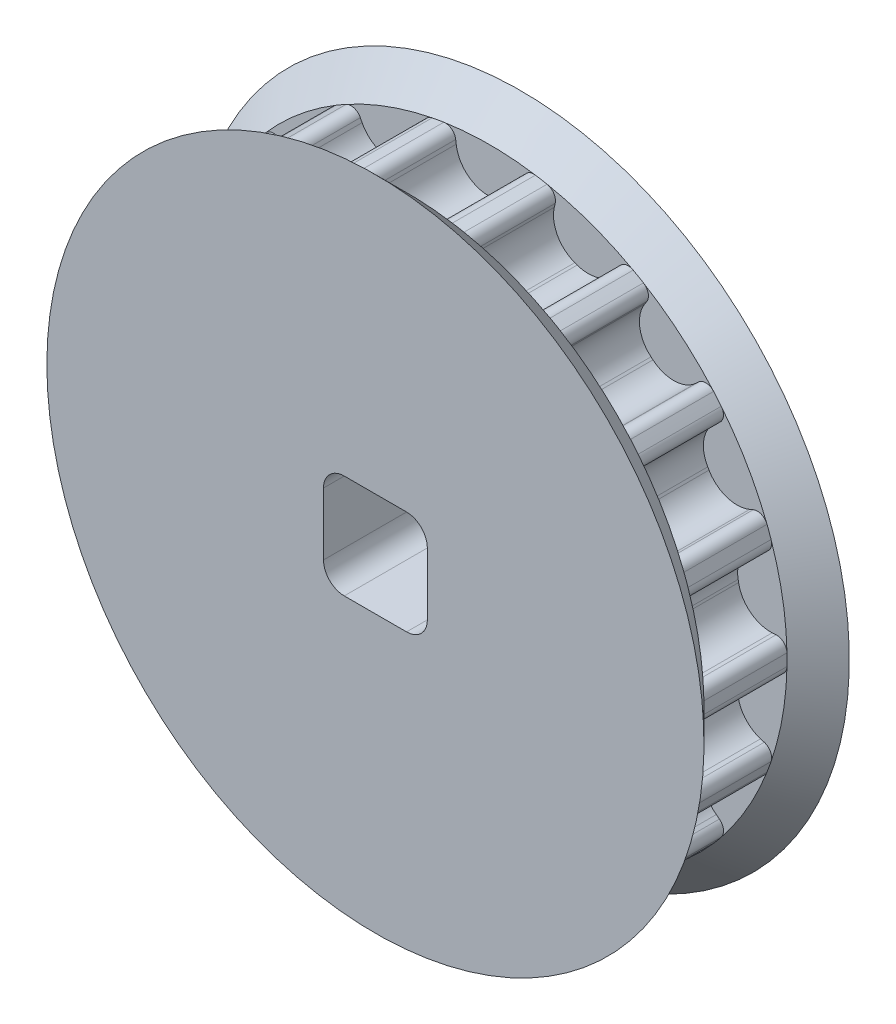
SolidWorks part; units mm, degrees
ref_plane "前视基准面" through (0, 0, 0) normal (0, 0, 1) x (1, 0, 0)
ref_plane "上视基准面" through (0, 0, 0) normal (0, 1, 0) x (1, 0, 0)
ref_plane "右视基准面" through (0, 0, 0) normal (1, 0, 0) x (0, 0, -1)
sketch "草图1" plane through (0, 0, 0) normal (0, 0, 1) x (1, 0, 0)
  line L0 (0, 0) -> (0, 14.3239) construction
  line L1 (0, 0) -> (-2.4873, 14.1063) construction
  line L2 (0, 0) -> (2.4873, 14.1063) construction
  line L3 (-1000, 12.1639) -> (49000, 12.1639) construction
  line L4 (-1.625, 14.2315) -> (-1.625, 13.6556) construction
  line L5 (-1.6329, 13.7199) -> (-1.61, 13.5338)
  line L6 (-0.0617, 12.1639) -> (0.0617, 12.1639)
  line L7 (1.6329, 13.7199) -> (1.61, 13.5338)
  line L8 (3.1581, 13.451) -> (3.1159, 13.2683)
  line L9 (4.1024, 11.4515) -> (4.2183, 11.4093)
  line L10 (6.2269, 12.334) -> (6.1418, 12.167)
  line L11 (7.5681, 11.5597) -> (7.466, 11.4024)
  line L12 (7.7716, 9.3578) -> (7.8661, 9.2785)
  line L13 (10.0699, 9.4605) -> (9.9327, 9.3326)
  line L14 (11.0654, 8.2741) -> (10.9156, 8.1613)
  line L15 (10.5034, 6.1354) -> (10.5651, 6.0286)
  line L16 (12.6983, 5.4458) -> (12.5257, 5.3726)
  line L17 (13.2279, 3.9905) -> (13.0486, 3.9357)
  line L18 (11.9684, 2.173) -> (11.9899, 2.0515)
  line L19 (13.795, 0.7743) -> (13.6078, 0.7645)
  line L20 (13.795, -0.7743) -> (13.6078, -0.7645)
  line L21 (11.9899, -2.0515) -> (11.9684, -2.173)
  line L22 (13.2279, -3.9905) -> (13.0486, -3.9357)
  line L23 (12.6983, -5.4458) -> (12.5257, -5.3726)
  line L24 (10.5651, -6.0286) -> (10.5034, -6.1354)
  line L25 (11.0654, -8.2741) -> (10.9156, -8.1613)
  line L26 (10.0699, -9.4605) -> (9.9327, -9.3326)
  line L27 (7.8661, -9.2785) -> (7.7716, -9.3578)
  line L28 (7.5681, -11.5597) -> (7.466, -11.4024)
  line L29 (6.2269, -12.334) -> (6.1418, -12.167)
  line L30 (4.2183, -11.4093) -> (4.1024, -11.4515)
  line L31 (3.1581, -13.451) -> (3.1159, -13.2683)
  line L32 (1.6329, -13.7199) -> (1.61, -13.5338)
  line L33 (0.0617, -12.1639) -> (-0.0617, -12.1639)
  line L34 (-1.6329, -13.7199) -> (-1.61, -13.5338)
  line L35 (-3.1581, -13.451) -> (-3.1159, -13.2683)
  line L36 (-4.1024, -11.4515) -> (-4.2183, -11.4093)
  line L37 (-6.2269, -12.334) -> (-6.1418, -12.167)
  line L38 (-7.5681, -11.5597) -> (-7.466, -11.4024)
  line L39 (-7.7716, -9.3578) -> (-7.8661, -9.2785)
  line L40 (-10.0699, -9.4605) -> (-9.9327, -9.3326)
  line L41 (-11.0654, -8.2741) -> (-10.9156, -8.1613)
  line L42 (-10.5034, -6.1354) -> (-10.5651, -6.0286)
  line L43 (-12.6983, -5.4458) -> (-12.5257, -5.3726)
  line L44 (-13.2279, -3.9905) -> (-13.0486, -3.9357)
  line L45 (-11.9684, -2.173) -> (-11.9899, -2.0515)
  line L46 (-13.795, -0.7743) -> (-13.6078, -0.7645)
  line L47 (-13.795, 0.7743) -> (-13.6078, 0.7645)
  line L48 (-11.9899, 2.0515) -> (-11.9684, 2.173)
  line L49 (-13.2279, 3.9905) -> (-13.0486, 3.9357)
  line L50 (-12.6983, 5.4458) -> (-12.5257, 5.3726)
  line L51 (-10.5651, 6.0286) -> (-10.5034, 6.1354)
  line L52 (-11.0654, 8.2741) -> (-10.9156, 8.1613)
  line L53 (-10.0699, 9.4605) -> (-9.9327, 9.3326)
  line L54 (-7.8661, 9.2785) -> (-7.7716, 9.3578)
  line L55 (-7.5681, 11.5597) -> (-7.466, 11.4024)
  line L56 (-6.2269, 12.334) -> (-6.1418, 12.167)
  line L57 (-4.2183, 11.4093) -> (-4.1024, 11.4515)
  line L58 (-3.1581, 13.451) -> (-3.1159, 13.2683)
  arc A0 (2.4873, 14.1063) -> (-2.4873, 14.1063) centre (0, 0) ccw construction
  circle A1 centre (0, 0) radius 13.7519 construction
  arc A2 (-2.4873, 14.1063) -> (-2.2062, 14.153) centre (0, 0) cw
  arc A3 (-1.6329, 13.7199) -> (-2.2062, 14.153) centre (-2.1292, 13.659) ccw
  arc A4 (-1.61, 13.5338) -> (-0.0617, 12.1639) centre (-0.0617, 13.7239) ccw
  arc A5 (1.61, 13.5338) -> (0.0617, 12.1639) centre (0.0617, 13.7239) cw
  arc A6 (1.6329, 13.7199) -> (2.2062, 14.153) centre (2.1292, 13.659) cw
  arc A7 (2.4873, 14.1063) -> (2.2062, 14.153) centre (0, 0) ccw
  arc A8 (2.4873, 14.1063) -> (2.7675, 14.0541) centre (0, 0) cw
  arc A9 (3.1581, 13.451) -> (2.7675, 14.0541) centre (2.6709, 13.5635) ccw
  arc A10 (3.1159, 13.2683) -> (4.1024, 11.4515) centre (4.6359, 12.9174) ccw
  arc A11 (6.1418, 12.167) -> (4.2183, 11.4093) centre (4.7518, 12.8752) cw
  arc A12 (6.2269, 12.334) -> (6.9138, 12.5449) centre (6.6724, 12.107) cw
  arc A13 (7.162, 12.4049) -> (6.9138, 12.5449) centre (0, 0) ccw
  arc A14 (7.162, 12.4049) -> (7.4074, 12.26) centre (0, 0) cw
  arc A15 (7.5681, 11.5597) -> (7.4074, 12.26) centre (7.1488, 11.832) ccw
  arc A16 (7.466, 11.4024) -> (7.7716, 9.3578) centre (8.7743, 10.5528) ccw
  arc A17 (9.9327, 9.3326) -> (7.8661, 9.2785) centre (8.8688, 10.4735) cw
  arc A18 (10.0699, 9.4605) -> (10.7874, 9.4237) centre (10.4109, 9.0948) cw
  arc A19 (10.9728, 9.2073) -> (10.7874, 9.4237) centre (0, 0) ccw
  arc A20 (10.9728, 9.2073) -> (11.1538, 8.9871) centre (0, 0) cw
  arc A21 (11.0654, 8.2741) -> (11.1538, 8.9871) centre (10.7644, 8.6734) ccw
  arc A22 (10.9156, 8.1613) -> (10.5034, 6.1354) centre (11.8544, 6.9154) ccw
  arc A23 (12.5257, 5.3726) -> (10.5651, 6.0286) centre (11.9161, 6.8086) cw
  arc A24 (12.6983, 5.4458) -> (13.36, 5.1659) centre (12.8936, 4.9856) cw
  arc A25 (13.4601, 4.8991) -> (13.36, 5.1659) centre (0, 0) ccw
  arc A26 (13.4601, 4.8991) -> (13.5549, 4.6303) centre (0, 0) cw
  arc A27 (13.2279, 3.9905) -> (13.5549, 4.6303) centre (13.0818, 4.4687) ccw
  arc A28 (13.0486, 3.9357) -> (11.9684, 2.173) centre (13.5047, 2.4439) ccw
  arc A29 (13.6078, 0.7645) -> (11.9899, 2.0515) centre (13.5262, 2.3224) cw
  arc A30 (13.795, 0.7743) -> (14.3211, 0.285) centre (13.8212, 0.275) cw
  arc A31 (14.3239, 0) -> (14.3211, 0.285) centre (0, 0) ccw
  arc A32 (14.3239, 0) -> (14.3211, -0.285) centre (0, 0) cw
  arc A33 (13.795, -0.7743) -> (14.3211, -0.285) centre (13.8212, -0.275) ccw
  arc A34 (13.6078, -0.7645) -> (11.9899, -2.0515) centre (13.5262, -2.3224) ccw
  arc A35 (13.0486, -3.9357) -> (11.9684, -2.173) centre (13.5047, -2.4439) cw
  arc A36 (13.2279, -3.9905) -> (13.5549, -4.6303) centre (13.0818, -4.4687) cw
  arc A37 (13.4601, -4.8991) -> (13.5549, -4.6303) centre (0, 0) ccw
  arc A38 (13.4601, -4.8991) -> (13.36, -5.1659) centre (0, 0) cw
  arc A39 (12.6983, -5.4458) -> (13.36, -5.1659) centre (12.8936, -4.9856) ccw
  arc A40 (12.5257, -5.3726) -> (10.5651, -6.0286) centre (11.9161, -6.8086) ccw
  arc A41 (10.9156, -8.1613) -> (10.5034, -6.1354) centre (11.8544, -6.9154) cw
  arc A42 (11.0654, -8.2741) -> (11.1538, -8.9871) centre (10.7644, -8.6734) cw
  arc A43 (10.9728, -9.2073) -> (11.1538, -8.9871) centre (0, 0) ccw
  arc A44 (10.9728, -9.2073) -> (10.7874, -9.4237) centre (0, 0) cw
  arc A45 (10.0699, -9.4605) -> (10.7874, -9.4237) centre (10.4109, -9.0948) ccw
  arc A46 (9.9327, -9.3326) -> (7.8661, -9.2785) centre (8.8688, -10.4735) ccw
  arc A47 (7.466, -11.4024) -> (7.7716, -9.3578) centre (8.7743, -10.5528) cw
  arc A48 (7.5681, -11.5597) -> (7.4074, -12.26) centre (7.1488, -11.832) cw
  arc A49 (7.162, -12.4049) -> (7.4074, -12.26) centre (0, 0) ccw
  arc A50 (7.162, -12.4049) -> (6.9138, -12.5449) centre (0, 0) cw
  arc A51 (6.2269, -12.334) -> (6.9138, -12.5449) centre (6.6724, -12.107) ccw
  arc A52 (6.1418, -12.167) -> (4.2183, -11.4093) centre (4.7518, -12.8752) ccw
  arc A53 (3.1159, -13.2683) -> (4.1024, -11.4515) centre (4.6359, -12.9174) cw
  arc A54 (3.1581, -13.451) -> (2.7675, -14.0541) centre (2.6709, -13.5635) cw
  arc A55 (2.4873, -14.1063) -> (2.7675, -14.0541) centre (0, 0) ccw
  arc A56 (2.4873, -14.1063) -> (2.2062, -14.153) centre (0, 0) cw
  arc A57 (1.6329, -13.7199) -> (2.2062, -14.153) centre (2.1292, -13.659) ccw
  arc A58 (1.61, -13.5338) -> (0.0617, -12.1639) centre (0.0617, -13.7239) ccw
  arc A59 (-1.61, -13.5338) -> (-0.0617, -12.1639) centre (-0.0617, -13.7239) cw
  arc A60 (-1.6329, -13.7199) -> (-2.2062, -14.153) centre (-2.1292, -13.659) cw
  arc A61 (-2.4873, -14.1063) -> (-2.2062, -14.153) centre (0, 0) ccw
  arc A62 (-2.4873, -14.1063) -> (-2.7675, -14.0541) centre (0, 0) cw
  arc A63 (-3.1581, -13.451) -> (-2.7675, -14.0541) centre (-2.6709, -13.5635) ccw
  arc A64 (-3.1159, -13.2683) -> (-4.1024, -11.4515) centre (-4.6359, -12.9174) ccw
  arc A65 (-6.1418, -12.167) -> (-4.2183, -11.4093) centre (-4.7518, -12.8752) cw
  arc A66 (-6.2269, -12.334) -> (-6.9138, -12.5449) centre (-6.6724, -12.107) cw
  arc A67 (-7.162, -12.4049) -> (-6.9138, -12.5449) centre (0, 0) ccw
  arc A68 (-7.162, -12.4049) -> (-7.4074, -12.26) centre (0, 0) cw
  arc A69 (-7.5681, -11.5597) -> (-7.4074, -12.26) centre (-7.1488, -11.832) ccw
  arc A70 (-7.466, -11.4024) -> (-7.7716, -9.3578) centre (-8.7743, -10.5528) ccw
  arc A71 (-9.9327, -9.3326) -> (-7.8661, -9.2785) centre (-8.8688, -10.4735) cw
  arc A72 (-10.0699, -9.4605) -> (-10.7874, -9.4237) centre (-10.4109, -9.0948) cw
  arc A73 (-10.9728, -9.2073) -> (-10.7874, -9.4237) centre (0, 0) ccw
  arc A74 (-10.9728, -9.2073) -> (-11.1538, -8.9871) centre (0, 0) cw
  arc A75 (-11.0654, -8.2741) -> (-11.1538, -8.9871) centre (-10.7644, -8.6734) ccw
  arc A76 (-10.9156, -8.1613) -> (-10.5034, -6.1354) centre (-11.8544, -6.9154) ccw
  arc A77 (-12.5257, -5.3726) -> (-10.5651, -6.0286) centre (-11.9161, -6.8086) cw
  arc A78 (-12.6983, -5.4458) -> (-13.36, -5.1659) centre (-12.8936, -4.9856) cw
  arc A79 (-13.4601, -4.8991) -> (-13.36, -5.1659) centre (0, 0) ccw
  arc A80 (-13.4601, -4.8991) -> (-13.5549, -4.6303) centre (0, 0) cw
  arc A81 (-13.2279, -3.9905) -> (-13.5549, -4.6303) centre (-13.0818, -4.4687) ccw
  arc A82 (-13.0486, -3.9357) -> (-11.9684, -2.173) centre (-13.5047, -2.4439) ccw
  arc A83 (-13.6078, -0.7645) -> (-11.9899, -2.0515) centre (-13.5262, -2.3224) cw
  arc A84 (-13.795, -0.7743) -> (-14.3211, -0.285) centre (-13.8212, -0.275) cw
  arc A85 (-14.3239, 0) -> (-14.3211, -0.285) centre (0, 0) ccw
  arc A86 (-14.3239, 0) -> (-14.3211, 0.285) centre (0, 0) cw
  arc A87 (-13.795, 0.7743) -> (-14.3211, 0.285) centre (-13.8212, 0.275) ccw
  arc A88 (-13.6078, 0.7645) -> (-11.9899, 2.0515) centre (-13.5262, 2.3224) ccw
  arc A89 (-13.0486, 3.9357) -> (-11.9684, 2.173) centre (-13.5047, 2.4439) cw
  arc A90 (-13.2279, 3.9905) -> (-13.5549, 4.6303) centre (-13.0818, 4.4687) cw
  arc A91 (-13.4601, 4.8991) -> (-13.5549, 4.6303) centre (0, 0) ccw
  arc A92 (-13.4601, 4.8991) -> (-13.36, 5.1659) centre (0, 0) cw
  arc A93 (-12.6983, 5.4458) -> (-13.36, 5.1659) centre (-12.8936, 4.9856) ccw
  arc A94 (-12.5257, 5.3726) -> (-10.5651, 6.0286) centre (-11.9161, 6.8086) ccw
  arc A95 (-10.9156, 8.1613) -> (-10.5034, 6.1354) centre (-11.8544, 6.9154) cw
  arc A96 (-11.0654, 8.2741) -> (-11.1538, 8.9871) centre (-10.7644, 8.6734) cw
  arc A97 (-10.9728, 9.2073) -> (-11.1538, 8.9871) centre (0, 0) ccw
  arc A98 (-10.9728, 9.2073) -> (-10.7874, 9.4237) centre (0, 0) cw
  arc A99 (-10.0699, 9.4605) -> (-10.7874, 9.4237) centre (-10.4109, 9.0948) ccw
  arc A100 (-9.9327, 9.3326) -> (-7.8661, 9.2785) centre (-8.8688, 10.4735) ccw
  arc A101 (-7.466, 11.4024) -> (-7.7716, 9.3578) centre (-8.7743, 10.5528) cw
  arc A102 (-7.5681, 11.5597) -> (-7.4074, 12.26) centre (-7.1488, 11.832) cw
  arc A103 (-7.162, 12.4049) -> (-7.4074, 12.26) centre (0, 0) ccw
  arc A104 (-7.162, 12.4049) -> (-6.9138, 12.5449) centre (0, 0) cw
  arc A105 (-6.2269, 12.334) -> (-6.9138, 12.5449) centre (-6.6724, 12.107) ccw
  arc A106 (-6.1418, 12.167) -> (-4.2183, 11.4093) centre (-4.7518, 12.8752) ccw
  arc A107 (-3.1159, 13.2683) -> (-4.1024, 11.4515) centre (-4.6359, 12.9174) cw
  arc A108 (-3.1581, 13.451) -> (-2.7675, 14.0541) centre (-2.6709, 13.5635) cw
  arc A109 (-2.4873, 14.1063) -> (-2.7675, 14.0541) centre (0, 0) ccw
  point P17 (-1.6947, 14.2233)
  point P20 (-1.4418, 12.1639)
  point P22 (0, 12.1639)
  point P38 (4.1603, 11.4304)
  point P53 (7.8188, 9.3181)
  point P68 (10.5343, 6.082)
  point P83 (11.9791, 2.1122)
  point P98 (11.9791, -2.1122)
  point P113 (10.5343, -6.082)
  point P128 (7.8188, -9.3181)
  point P143 (4.1603, -11.4304)
  point P158 (0, -12.1639)
  point P173 (-4.1603, -11.4304)
  point P188 (-7.8188, -9.3181)
  point P193 (0, 0)
  point P202 (-10.5343, -6.082)
  point P217 (-11.9791, -2.1122)
  point P232 (-11.9791, 2.1122)
  point P247 (-10.5343, 6.082)
  point P262 (-7.8188, 9.3181)
  point P277 (-4.1603, 11.4304)
  dimension "齿顶圆角半径" = 0.5
  dimension "齿槽圆弧半径" = 1.56
  dimension "半齿角" = 10
  dimension "节顶距" = 0.572
  dimension "齿槽深" = 2.16
  dimension "半齿槽宽" = 1.625
  dimension "D6" = 7
  dimension "槽型弧长" = 5
  dimension "D9" = 18
extrude "凸台-拉伸1" add sketch "草图1" along normal mid plane 4 contours A2 A73 A72 L40 A71 L39 A70 L38 A69 A68 A67 A66 L37 A65 L36 A64 L35 A63 A62 A61 A60 L34 A59 L33 A58 L32 A57 A56 A55 A54 L31 A53 L30 A52 L29 A51 A50 A49 A48 L28 A47 L27 A46 L26 A45 A44 A43 A42 L25 A41 L24 region at (0, 0, 0)
sketch "草图3" plane through (0, 0, -2) normal (0, 0, -1) x (-1, 0, 0)
  circle A0 centre (0, 0) radius 15.8239
  dimension "翻边直径" = 31.6479
extrude "凸台-拉伸2" add sketch "草图3" along normal blind 1.5
chamfer "倒角1" distance 1.5 angle 45 1 edges at (-15.8239, 0, -2)
mirror "镜向10" about plane through (0, 0, 0) normal (0, 0, 1) of "倒角1", "凸台-拉伸2"
sketch "草图4" plane through (0, 0, -3.5) normal (0, 0, -1) x (-1, 0, 0)
  line L1 (1.5, 2.5) -> (-1.5, 2.5)
  line L2 (-2.5, 1.5) -> (-2.5, -1.5)
  line L3 (-1.5, -2.5) -> (1.5, -2.5)
  line L4 (2.5, -1.5) -> (2.5, 1.5)
  circle A0 centre (0, 0) radius 2.5 construction
  arc A1 (-1.5, 2.5) -> (-2.5, 1.5) centre (-1.5, 1.5) ccw
  arc A2 (-2.5, -1.5) -> (-1.5, -2.5) centre (-1.5, -1.5) ccw
  arc A3 (1.5, -2.5) -> (2.5, -1.5) centre (1.5, -1.5) ccw
  arc A4 (1.5, 2.5) -> (2.5, 1.5) centre (1.5, 1.5) cw
  dimension "D2" = 1
  dimension "D1" = 5
extrude "切除-拉伸1" cut sketch "草图4" against normal through all
